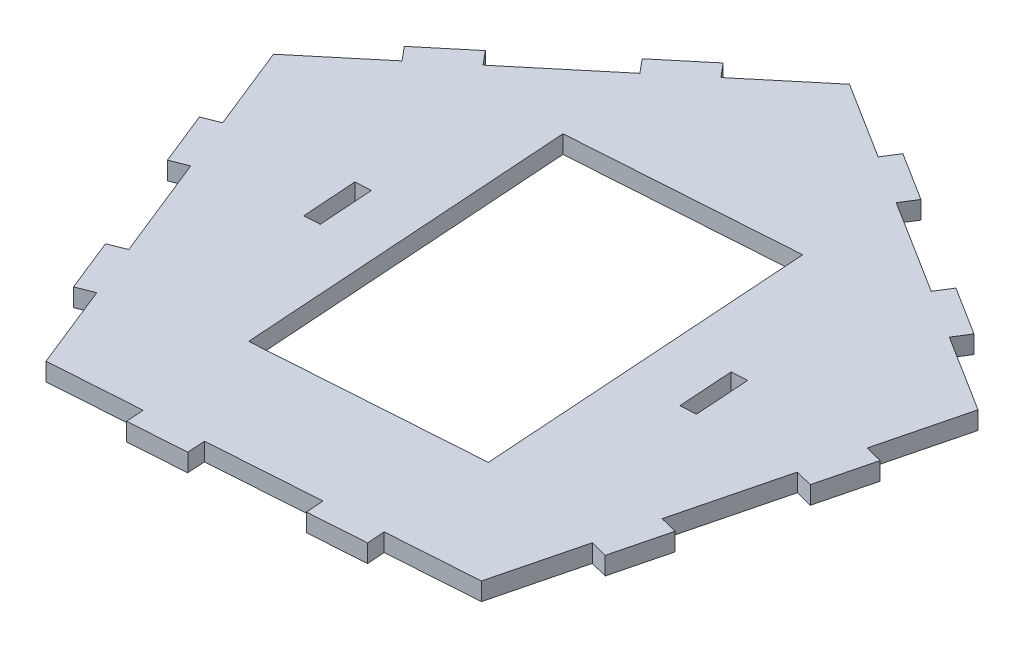
SolidWorks part; units mm, degrees
ref_plane "Front Plane" through (0, 0, 0) normal (0, 0, 1) x (1, 0, 0)
ref_plane "Top Plane" through (0, 0, 0) normal (0, 1, 0) x (1, 0, 0)
ref_plane "Right Plane" through (0, 0, 0) normal (1, 0, 0) x (0, 0, -1)
sketch "Sketch1" plane through (0, 0, 0) normal (0, 1, 0) x (1, 0, 0)
  line L1 (-59.9258, 15.1181) -> (-32.8962, -52.3211)
  line L2 (-32.8962, -52.3211) -> (39.5948, -47.4543)
  line L3 (39.5948, -47.4543) -> (57.3672, 22.9927)
  line L4 (57.3672, 22.9927) -> (-4.14, 61.6646)
  line L5 (-4.14, 61.6646) -> (-59.9258, 15.1181)
  circle A0 centre (0, 0) radius 50 construction
  dimension "D1" = 100
extrude "Boss-Extrude1" add sketch "Sketch1" along normal blind 3.18
ref_axis "Axis" through (0, 3.339, 0) along (0, -1, 0)
sketch "Axis Check" plane through (0, 3.18, 0) normal (0, 1, 0) x (1, 0, 0)
  line L0 (3.3493, -49.8877) -> (-4.14, 61.6646) construction
  line L1 (-32.8962, -52.3211) -> (39.5948, -47.4543) construction
  line L2 (57.3672, 22.9927) -> (-46.411, -18.6015) construction
  line L3 (-59.9258, 15.1181) -> (-32.8962, -52.3211) construction
  line L4 (-32.0329, 38.3913) -> (39.5948, -47.4543) construction
  line L5 (-4.14, 61.6646) -> (-59.9258, 15.1181) construction
  line L6 (-59.9258, 15.1181) -> (48.481, -12.2308) construction
  line L7 (39.5948, -47.4543) -> (57.3672, 22.9927) construction
  line L8 (-32.8962, -52.3211) -> (26.6136, 42.3287) construction
  line L9 (57.3672, 22.9927) -> (-4.14, 61.6646) construction
sketch "Sketch2" plane through (0, 0, 0) normal (0, -1, 0) x (1, 0, 0)
  line L0 (-53.8107, 0.1392) -> (-50.859, -1.0438)
  line L1 (-53.8107, 0.1392) -> (-50.1723, 9.2172)
  line L2 (-50.859, -1.0438) -> (-47.2205, 8.0342)
  line L3 (-50.1723, 9.2172) -> (-47.2205, 8.0342)
  line L4 (-59.9258, -15.1181) -> (-32.8962, 52.3211) construction
  line L5 (-42.6498, 27.9858) -> (-39.0113, 37.0638)
  line L6 (-42.6498, 27.9858) -> (-39.6981, 26.8028)
  line L7 (-39.0113, 37.0638) -> (-36.0596, 35.8808)
  line L8 (-39.6981, 26.8028) -> (-36.0596, 35.8808)
  line L9 (-46.411, 18.6015) -> (-19.2439, 7.7129) construction
  line L10 (-40.8306, 32.5248) -> (-37.8788, 31.3418) construction
  dimension "D1" = 3.18
  dimension "D2" = 9.78
  dimension "D3" = 10.11
extrude "Cut F" [suppressed] cut sketch "Sketch2" against normal through all
sketch "Sketch4" [suppressed] plane through (0, 3.18, 0) normal (0, 1, 0) x (1, 0, 0)
  line L9 (26.6136, 42.3287) -> (-26.6136, -42.3287) construction
  line L10 (57.3672, 22.9927) -> (-4.14, 61.6646) construction
  line L11 (-27.7286, -6.3206) -> (-6.3206, 27.7286)
  line L12 (-27.7286, -6.3206) -> (6.3206, -27.7286)
  line L13 (-6.3206, 27.7286) -> (27.7286, 6.3206)
  line L14 (6.3206, -27.7286) -> (27.7286, 6.3206)
  line L15 (-27.7286, -6.3206) -> (27.7286, 6.3206) construction
  line L16 (-6.3206, 27.7286) -> (6.3206, -27.7286) construction
  line L20 (0, 0) -> (39.0006, -24.5211) construction
  circle A0 centre (-14.9622, -23.7972) radius 3.25
  circle A1 centre (23.7972, -14.9622) radius 3.25
  point P5 (0, 0)
  point P6 (-14.9622, -23.7972)
  dimension "D3" = 6.5
  dimension "D1" = 40.22
  dimension "D2" = 40.22
  dimension "D4" = 8
  dimension "D5" = 8
extrude "Top Cut" [suppressed] cut sketch "Sketch4" against normal blind 10
sketch "Sketch7" [suppressed] plane through (0, 3.18, 0) normal (0, 1, 0) x (1, 0, 0)
  line L0 (0, 0) -> (26.6136, 42.3287) construction
  line L1 (57.3672, 22.9927) -> (-4.14, 61.6646) construction
  line L2 (1.0645, 1.6931) -> (-22.7326, 16.6553) construction
  line L3 (-6.1086, 1.4782) -> (-24.8617, 13.269) construction
  line L5 (-6.3206, 27.7286) -> (-27.7286, -6.3206) construction
  circle A0 centre (-22.7326, 16.6553) radius 1
  circle A1 centre (-24.8617, 13.269) radius 1
  dimension "D5" = 2
  dimension "D1" = 4
  dimension "D2" = 2
  dimension "D3" = 8
  dimension "D4" = 8
extrude "Top Cut 2" [suppressed] cut sketch "Sketch7" against normal through all
sketch "Sketch8" plane through (0, 3.18, 0) normal (0, 1, 0) x (1, 0, 0)
  line L0 (3.3493, -49.8877) -> (-4.14, 61.6646) construction
  line L5 (-32.8962, -52.3211) -> (39.5948, -47.4543) construction
  line L6 (-17.9455, -31.2723) -> (21.9647, -28.5929)
  line L11 (-17.9455, -31.2723) -> (-21.9647, 28.5929)
  line L12 (21.9647, -28.5929) -> (17.9455, 31.2723)
  line L13 (-21.9647, 28.5929) -> (17.9455, 31.2723)
  point P4 (1.4955, -22.2759)
  dimension "D1" = 60
  dimension "D2" = 40
  dimension "D3" = 20
extrude "Bottom Cut" cut sketch "Sketch8" against normal blind 10
sketch "Sketch9" plane through (0, 3.18, 0) normal (0, 1, 0) x (1, 0, 0)
  line L0 (19.9551, 1.3397) -> (-19.9551, -1.3397) construction
  line L1 (21.9647, -28.5929) -> (17.9455, 31.2723) construction
  line L2 (-21.9647, 28.5929) -> (-17.9455, -31.2723) construction
  line L3 (-19.9551, -1.3397) -> (-44.4689, -2.9855) construction
  line L4 (19.9551, 1.3397) -> (42.6839, 2.8657) construction
  line L5 (-32.8962, -52.3211) -> (39.5948, -47.4543) construction
  line L6 (-29.6051, -6.8886) -> (-32.3788, -7.0748)
  line L7 (-29.6051, -6.8886) -> (-30.2602, 2.8694)
  line L8 (-30.2602, 2.8694) -> (-33.0339, 2.6832)
  line L9 (-32.3788, -7.0748) -> (-33.0339, 2.6832)
  line L10 (-29.6051, -6.8886) -> (-33.0339, 2.6832) construction
  line L11 (-30.2602, 2.8694) -> (-32.3788, -7.0748) construction
  line L12 (33.0339, -2.6832) -> (30.2602, -2.8694)
  line L13 (33.0339, -2.6832) -> (32.3788, 7.0748)
  line L14 (32.3788, 7.0748) -> (29.6051, 6.8886)
  line L15 (30.2602, -2.8694) -> (29.6051, 6.8886)
  line L16 (33.0339, -2.6832) -> (29.6051, 6.8886) construction
  line L17 (32.3788, 7.0748) -> (30.2602, -2.8694) construction
  line L18 (-32.8962, -52.3211) -> (39.5948, -47.4543) construction
  point P6 (-31.3195, -2.1027)
  point P13 (31.3195, 2.1027)
  dimension "D1" = 9.78
  dimension "D4" = 9.78
  dimension "D5" = 10
  dimension "D6" = 10
  dimension "D3" = 2.78
  dimension "D2" = 2.78
extrude "Battery Holder Cut" cut sketch "Sketch9" against normal blind 3.18
sketch "Sketch3" plane through (0, 3.18, 0) normal (0, 1, 0) x (1, 0, 0)
  line L0 (0, 0) -> (-40.9819, 49.1167) construction
  line L1 (-49.5112, 27.9494) -> (-45.4366, 23.066)
  line L3 (-45.4366, 23.066) -> (-37.5894, 29.6135)
  line L4 (-41.664, 34.4969) -> (-37.5894, 29.6135)
  line L5 (-4.14, 61.6646) -> (-59.9258, 15.1181) construction
  line L6 (-71.9961, 5.0469) -> (-69.9588, 2.6052)
  line L7 (-71.9961, 5.0469) -> (-47.4739, 25.5077)
  line L14 (-26.4764, 47.1691) -> (-22.4018, 42.2857)
  line L16 (-22.4018, 42.2857) -> (-14.5546, 48.8333)
  line L17 (-18.6292, 53.7166) -> (-14.5546, 48.8333)
  line L18 (-42.539, 27.5695) -> (-41.513, 26.3398) construction
  line L19 (-49.5112, 27.9494) -> (-41.664, 34.4969)
  line L21 (-26.4764, 47.1691) -> (-18.6292, 53.7166)
  line L22 (-16.5919, 51.275) -> (4.7866, 69.1127)
  line L23 (-39.6267, 32.0552) -> (-24.4391, 44.7274)
  line M18 (-4.14, 61.6646) -> (-59.9258, 15.1181)
  dimension "D1" = 3.18
  dimension "D2" = 10.22
  dimension "D3" = 9.89
  dimension "D4" = 100
extrude "Extrude M" add sketch "Sketch3" against normal up to surface (3.18 mm away) contours L21 L14 L7 L17 | L19 L1 L4 M18 region at (-44.5689, 3.18, -30.0023) region at (-21.5341, 3.18, -49.222) up to face at (-31.3195, 0, 2.1027)
pattern_circular "Circle F" [suppressed] count 5 over 360 about axis through (0, 3.339, 0) along (0, -1, 0) of bodies 173
pattern_circular "Circle M" count 5 over 360 about axis through (0, 3.339, 0) along (0, -1, 0) of "Extrude M"
pattern_circular "Circle Side F" [suppressed] count 5 over 360 about axis through (0, 3.339, 0) along (0, -1, 0) of bodies 173
pattern_circular "Circle Side M" [suppressed] count 5 over 360 about axis through (0, 3.339, 0) along (0, -1, 0) of bodies 168
equation "\"kerf\"= .22mm"
equation "\"tabWidthF\"= 10 - \"kerf\""
equation "\"tabThickness\"= 3.18"
equation "\"D1@Sketch2\"=\"tabThickness\""
equation "\"tabWidthM\"= 10 + \"kerf\""
equation "\"halfkerf\"= \"kerf\" / 2.00mm"
equation "\"D1@Sketch9\"=\"tabWidthF\""
equation "\"D4@Sketch9\"=\"tabWidthF\""
equation "\"D1@Battery Holder Cut\" = \"tabThickness\""
equation "\"tabLength\" = \"kerf\" + 12"
